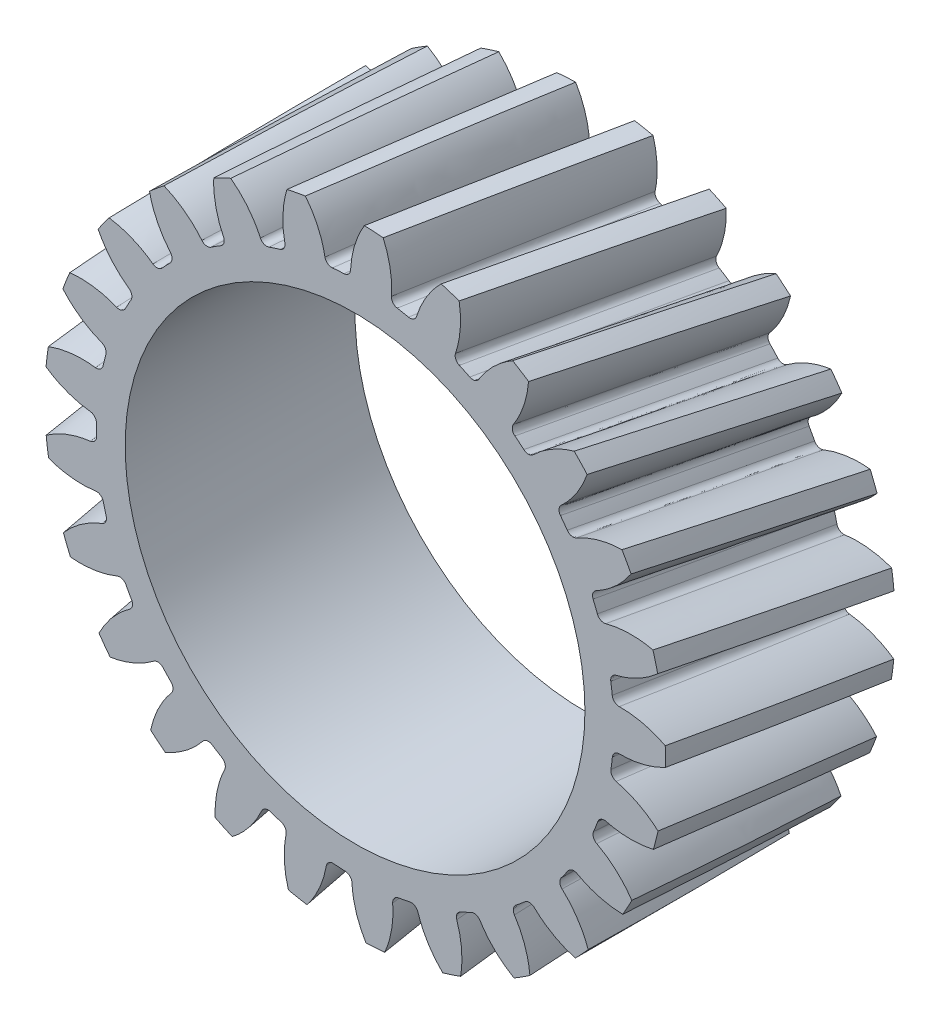
SolidWorks part; units mm, degrees
material "Plain Carbon Steel"
ref_plane "Front Plane" through (0, 0, 0) normal (0, 0, 1) x (1, 0, 0)
ref_plane "Top Plane" through (0, 0, 0) normal (0, 1, 0) x (1, 0, 0)
ref_plane "Right Plane" through (0, 0, 0) normal (1, 0, 0) x (0, 0, -1)
sketch "Sketch1" plane through (0, 0, 0) normal (0, 0, 1) x (1, 0, 0)
  circle A0 centre (0, 0) radius 25
  circle A1 centre (0, 0) radius 27
  circle A2 centre (0, 0) radius 22.5
  dimension "D1" = 50
  dimension "D2" = 54
  dimension "D3" = 4.5
extrude "Boss-Extrude1" add sketch "Sketch1" along normal mid plane 20 contours A1
sketch "Sketch2" plane through (0, 0, 0) normal (0, 0, 1) x (1, 0, 0)
  line L0 (0, 0) -> (0, 27) construction
  line L1 (-1.5698, 24.9507) -> (1.5698, 24.9507) construction
  line L2 (0, 0) -> (-1.072, 22.4744) construction
  line L3 (-2.6344, 27.8758) -> (0, 20.6378) construction
  line L4 (0, 0) -> (3.384, 26.7871) construction
  line L5 (1.5698, 24.9507) -> (4.6845, 24.5572) construction
  circle A0 centre (0, 0) radius 27 construction
  arc A1 (-3.3153, 27.803) -> (-1.072, 22.4744) centre (-9.4743, 22.0737) cw
  arc A2 (3.3153, 27.803) -> (1.072, 22.4744) centre (9.4743, 22.0737) ccw
  circle A3 centre (0, 0) radius 22.5 construction
  arc A4 (1.072, 22.4744) -> (-1.072, 22.4744) centre (0, 0) ccw
  circle A7 centre (0, 0) radius 25 construction
  circle A8 centre (0, 0) radius 28
  arc A9 (3.3153, 27.803) -> (-3.3153, 27.803) centre (0, 0) ccw
  circle A10 centre (0, 0) radius 27 construction
  dimension "D2" = 20
  dimension "D3" = 7.2
  dimension "D1" = 1
sketch "Sketch3" plane through (0, 0, 0) normal (0, 1, 0) x (1, 0, 0)
  line L0 (-1.7633, -10) -> (1.7633, 10)
  line L3 (-27, -10) -> (27, -10) construction
  line L4 (27, 10) -> (-27, 10) construction
  line L5 (0, -27.5) -> (0, 27.5) construction
  point P6 (0, 0)
  dimension "D1" = 10
curve "Curve1"
sketch "Sketch4" plane through (0, 0, 10) normal (0, 0, 1) x (0.9979, 0.0653, 0)
  line L0 (0, 0) -> (0, 27) construction
  line L1 (-1.5698, 24.9507) -> (1.5698, 24.9507) construction
  line L2 (0, 0) -> (-1.072, 22.4744) construction
  line L3 (-2.6344, 27.8758) -> (0, 20.6378) construction
  line L4 (0, 0) -> (3.384, 26.7871) construction
  line L5 (1.5698, 24.9507) -> (4.6845, 24.5572) construction
  arc A1 (-3.3153, 27.803) -> (-1.072, 22.4744) centre (-9.4743, 22.0737) cw
  arc A2 (3.3153, 27.803) -> (1.072, 22.4744) centre (9.4743, 22.0737) ccw
  arc A4 (1.072, 22.4744) -> (-1.072, 22.4744) centre (0, 0) ccw
  arc A9 (3.3153, 27.803) -> (-3.3153, 27.803) centre (0, 0) ccw
sketch "Sketch5" plane through (0, 0, -10) normal (0, 0, 1) x (0.9979, -0.0653, 0)
  line L0 (0, 0) -> (0, 27) construction
  line L1 (-1.5698, 24.9507) -> (1.5698, 24.9507) construction
  line L2 (0, 0) -> (-1.072, 22.4744) construction
  line L3 (-2.6344, 27.8758) -> (0, 20.6378) construction
  line L4 (0, 0) -> (3.384, 26.7871) construction
  line L5 (1.5698, 24.9507) -> (4.6845, 24.5572) construction
  arc A1 (-3.3153, 27.803) -> (-1.072, 22.4744) centre (-9.4743, 22.0737) cw
  arc A2 (3.3153, 27.803) -> (1.072, 22.4744) centre (9.4743, 22.0737) ccw
  arc A4 (1.072, 22.4744) -> (-1.072, 22.4744) centre (0, 0) ccw
  arc A9 (3.3153, 27.803) -> (-3.3153, 27.803) centre (0, 0) ccw
loft "Cut-Loft1" cut profiles "Sketch4", "Sketch2", "Sketch5" start constraint default end constraint default
fillet "Fillet1" radius 0.6 2 edges
pattern_circular "CirPattern2" count 25 over 360 about axis through (0, 0, 10) along (0, 0, -1) of "Cut-Loft1", "Fillet1" reverse direction yes
sketch "Sketch6" plane through (0, 0, 0) normal (0, 0, 1) x (1, 0, 0)
  circle A0 centre (0, 0) radius 20
  dimension "D1" = 40
extrude "Cut-Extrude1" cut sketch "Sketch6" against normal mid plane 20
equation "\"module\"= 2mm"
equation "\"Number of teeth\"= 25"
equation "\"D2@Sketch1\"=(\"Number of teeth\" + 2) * \"module\""
equation "\"D3@Sketch1\"=\"module\" * if( \"module\"=>1.25,2.25,2.4)"
equation "\"D3@Sketch2\"=180/\"Number of teeth\""
